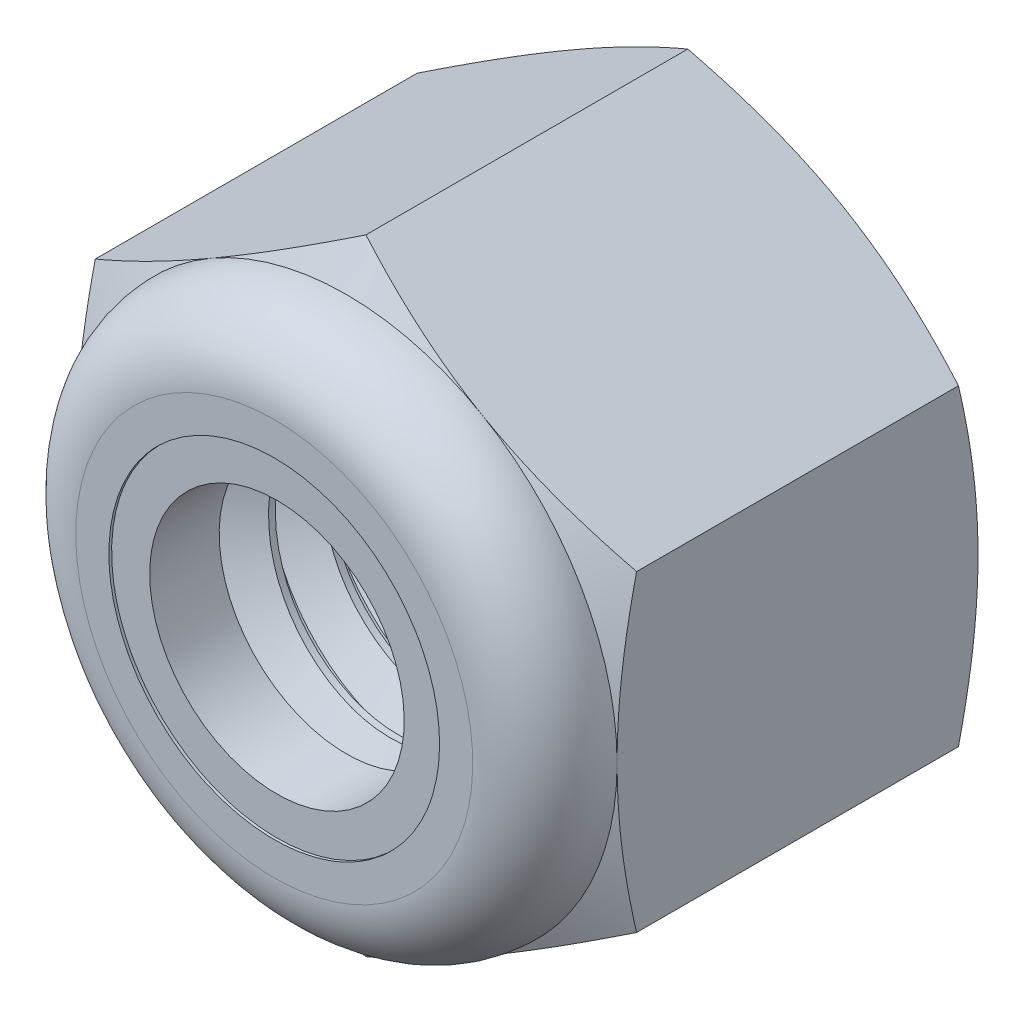
SolidWorks part; units mm, degrees
ref_plane "Front Plane" through (0, 0, 0) normal (0, 0, 1) x (1, 0, 0)
ref_plane "Top Plane" through (0, 0, 0) normal (0, 1, 0) x (1, 0, 0)
ref_plane "Right Plane" through (0, 0, 0) normal (1, 0, 0) x (0, 0, -1)
sketch "Sketch1" plane through (0, 0, 0) normal (0, 0, 1) x (1, 0, 0)
  line L1 (0, 5.7735) -> (-5, 2.8868)
  line L2 (-5, 2.8868) -> (-5, -2.8868)
  line L3 (-5, -2.8868) -> (0, -5.7735)
  line L4 (0, -5.7735) -> (5, -2.8868)
  line L5 (5, -2.8868) -> (5, 2.8868)
  line L6 (5, 2.8868) -> (0, 5.7735)
  circle A0 centre (0, 0) radius 5 construction
  circle A1 centre (0, 0) radius 3
  point P10 (0, -3)
  point P11 (0, 3)
  point P12 (0, 5)
  dimension "Thread Size" = 6
  dimension "Width" = 10
sketch "Sketch2" plane through (0, 0, 0) normal (1, 0, 0) x (0, 0, -1)
  line L0 (4, 0) -> (-4, 0) construction
  line L1 (-4, 3) -> (4, 3) construction
  line L2 (-3.95, -3.0086) -> (-5.27, -3.0086) construction
  line L3 (-4.9375, 3.1083) -> (-3.9375, 3.1083) construction
  line L4 (-3.9375, 3.1083) -> (-4.4375, 2.2422) construction
  line L5 (-4.4375, 2.2422) -> (-4.9375, 3.1083) construction
  line L6 (-4.875, 3) -> (-4, 3) construction
  line L7 (-4.5, 2.3505) -> (-4.375, 2.3505) construction
  line L8 (-4.4375, 2.3505) -> (-4.4375, 2.2422) construction
  line L9 (-4.4375, 3) -> (-4.4375, 3.1083) construction
  line L10 (-3.9687, 3.0541) -> (-4.9063, 3.0541)
  line L11 (-4.9063, 3.0541) -> (-4.5, 2.3505)
  line L12 (-4.5, 2.3505) -> (-4.375, 2.3505)
  line L13 (-4.375, 2.3505) -> (-3.9687, 3.0541)
  line L14 (4, 0) -> (5.27, 0)
  line L15 (5.27, 0) -> (5.27, 7.0435)
  line L16 (0, 7.0435) -> (0, 5.7735) construction
  line L17 (0, 5.7735) -> (0, 2.8868) construction
  line L18 (4, 5) -> (-2.6667, 5) construction
  line L19 (-4.5, -2.3505) -> (-4.375, -2.3505) construction
  line L20 (4, 5) -> (4, 0)
  line L21 (3.6393, 5.7735) -> (-2.306, 5.7735)
  line L22 (4, 5) -> (3.6393, 5.7735)
  line L23 (-4, 0) -> (-4, 3.6667) construction
  line L24 (-2.6667, 5) -> (-2.306, 5.7735)
  line L25 (5.27, 7.0435) -> (-5.27, 7.0435)
  line L26 (-4, 3.6667) -> (-5.27, 3.6667)
  line L27 (-5.27, 3.6667) -> (-5.27, 7.0435)
  line L28 (-3.95, 3.6667) -> (-3.95, 2.3505) construction
  line L29 (-3.95, 3.0086) -> (-5.27, 3.0086)
  line L30 (-5.27, 3.0086) -> (-5.27, 0)
  line L31 (-5.27, 0) -> (-2.6667, 0)
  line L32 (-2.6667, 0) -> (-2.6667, 4.95)
  line L33 (-3.95, 3.0086) -> (-3.95, 3.6667)
  arc A0 (-2.6667, 5) -> (-4, 3.6667) centre (-2.6667, 3.6667) ccw
  arc A1 (-2.6667, 4.95) -> (-3.95, 3.6667) centre (-2.6667, 3.6667) ccw
  point P4 (0, 0)
  point P18 (-4.4375, 3.0541)
  point P22 (-4.4375, 3.0541)
  point P33 (0, 5.7735)
  point P48 (-5.27, -3.0086)
  point P51 (-4.5, -2.3505)
  dimension "Height" = 8
  dimension "Pitch" = 1
  dimension "D1" = 0.125
  dimension "D2" = 1.27
  dimension "D3" = 25
  dimension "D4" = 1.3333
  dimension "D5" = 25
  dimension "D6" = 0.05
sketch "Sketch3" plane through (0, 0, 0) normal (0, 0, 1) x (1, 0, 0)
  line L0 (0, -5.7735) -> (5, -2.8868) construction
  line L1 (5, -2.8868) -> (5, 2.8868) construction
  line L2 (5, 2.8868) -> (0, 5.7735) construction
  line L3 (0, 5.7735) -> (-5, 2.8868) construction
  line L4 (-5, 2.8868) -> (-5, -2.8868) construction
  line L5 (-5, -2.8868) -> (0, -5.7735) construction
  line L6 (0, -5.7735) -> (5, -2.8868)
  line L7 (5, -2.8868) -> (5, 2.8868)
  line L8 (5, 2.8868) -> (0, 5.7735)
  line L9 (0, 5.7735) -> (-5, 2.8868)
  line L10 (-5, 2.8868) -> (-5, -2.8868)
  line L11 (-5, -2.8868) -> (0, -5.7735)
  circle A0 centre (0, 0) radius 3 construction
  circle A1 centre (0, 0) radius 3
extrude "Boss-Extrude1" add sketch "Sketch3" along normal mid plane 8
sketch "Sketch4" plane through (0, 0, 0) normal (1, 0, 0) x (0, 0, -1)
  line L0 (5.27, 7.0435) -> (-5.27, 7.0435) construction
  line L1 (-5.27, 3.6667) -> (-5.27, 7.0435) construction
  line L2 (-4, 3.6667) -> (-5.27, 3.6667) construction
  line L3 (-2.6667, 5) -> (-2.306, 5.7735) construction
  line L4 (3.6393, 5.7735) -> (-2.306, 5.7735) construction
  line L5 (4, 5) -> (3.6393, 5.7735) construction
  line L6 (4, 5) -> (4, 0) construction
  line L7 (4, 0) -> (5.27, 0) construction
  line L8 (5.27, 0) -> (5.27, 7.0435) construction
  line L9 (-5.27, 3.0086) -> (-5.27, 0) construction
  line L10 (-5.27, 0) -> (-2.6667, 0) construction
  line L11 (-2.6667, 0) -> (-2.6667, 4.95) construction
  line L12 (-3.95, 3.0086) -> (-3.95, 3.6667) construction
  line L13 (-3.95, 3.0086) -> (-5.27, 3.0086) construction
  line L14 (5.27, 7.0435) -> (-5.27, 7.0435)
  line L15 (-5.27, 3.6667) -> (-5.27, 7.0435)
  line L16 (-4, 3.6667) -> (-5.27, 3.6667)
  line L17 (-2.6667, 5) -> (-2.306, 5.7735)
  line L18 (3.6393, 5.7735) -> (-2.306, 5.7735)
  line L19 (4, 5) -> (3.6393, 5.7735)
  line L20 (4, 5) -> (4, 0)
  line L21 (4, 0) -> (5.27, 0)
  line L22 (5.27, 0) -> (5.27, 7.0435)
  line L23 (-5.27, 3.0086) -> (-5.27, 0)
  line L24 (-5.27, 0) -> (-2.6667, 0)
  line L25 (-2.6667, 0) -> (-2.6667, 4.95)
  line L26 (-3.95, 3.0086) -> (-3.95, 3.6667)
  line L27 (-3.95, 3.0086) -> (-5.27, 3.0086)
  arc A0 (-2.6667, 5) -> (-4, 3.6667) centre (-2.6667, 3.6667) ccw construction
  arc A1 (-2.6667, 4.95) -> (-3.95, 3.6667) centre (-2.6667, 3.6667) ccw construction
  arc A2 (-2.6667, 5) -> (-4, 3.6667) centre (-2.6667, 3.6667) ccw
  arc A3 (-2.6667, 4.95) -> (-3.95, 3.6667) centre (-2.6667, 3.6667) ccw
revolve "Cut-Revolve1" cut sketch "Sketch4" angle 360 about L0
sketch "Sketch5" plane through (0, 0, 0) normal (1, 0, 0) x (0, 0, -1)
  line L0 (-3.95, 3.6667) -> (-3.95, 2.3505) construction
  line L1 (-2.6667, 0) -> (-2.6667, 4.95) construction
  line L2 (-3.95, 3.6667) -> (-3.95, 2.3505)
  line L3 (-2.6667, 2.3505) -> (-2.6667, 4.95)
  line L4 (-3.95, 2.3505) -> (-2.6667, 2.3505)
  arc A0 (-2.6667, 4.95) -> (-3.95, 3.6667) centre (-2.6667, 3.6667) ccw construction
  arc A1 (-2.6667, 4.95) -> (-3.95, 3.6667) centre (-2.6667, 3.6667) ccw
revolve "Revolve1" add sketch "Sketch5" angle 360 about L0
sketch "Sketch6" plane through (0, 0, 4) normal (0, 0, 1) x (1, 0, 0)
  circle A0 centre (0, 0) radius 3 construction
  circle A1 centre (0, 0) radius 3
curve "Helix/Spiral1" pitch 1 height 9 radius 3 centre (0, 0, 4) axis (0, 0, -1) start towards (0, 1, 0)
sketch "Sketch7" plane through (0, 0, 0) normal (1, 0, 0) x (0, 0, -1)
  line L0 (-4.9063, 3.0541) -> (-4.5, 2.3505) construction
  line L1 (-4.5, 2.3505) -> (-4.375, 2.3505) construction
  line L2 (-4.375, 2.3505) -> (-3.9687, 3.0541) construction
  line L3 (-3.9687, 3.0541) -> (-4.9063, 3.0541) construction
  line L4 (-4.9063, 3.0541) -> (-4.5, 2.3505)
  line L5 (-4.5, 2.3505) -> (-4.375, 2.3505)
  line L6 (-4.375, 2.3505) -> (-3.9687, 3.0541)
  line L7 (-3.9687, 3.0541) -> (-4.9063, 3.0541)
sweep "Sweep1" add profiles "Sketch7" path "Helix/Spiral1"
sketch "Sketch8" plane through (0, 0, -4) normal (0, 0, -1) x (-1, 0, 0)
  circle A2 centre (0, 0) radius 3.0541
  point P2 (0, 3.0541)
extrude "Cut-Extrude1" cut sketch "Sketch8" along normal through all and the other way through all draft 60
sketch "Sketch9" plane through (0, 0, 2.6667) normal (0, 0, 1) x (1, 0, 0)
  circle A2 centre (0, 0) radius 3.0541
  circle A3 centre (0, 0) radius 2.3505 construction
  point P2 (0, 3.0541)
  point P4 (0, 2.3505)
extrude "Cut-Extrude2" cut sketch "Sketch9" along normal through all and the other way through all draft 60
equation "\"D1@Sketch2\" = \"Pitch@Sketch2\" / 8"
equation "\"D4@Sketch2\"=\"Height@Sketch2\"/6"
equation "\"D1@Boss-Extrude1\"=\"Height@Sketch2\""
equation "\"D3@Helix/Spiral1\"=\"Height@Sketch2\"+\"Pitch@Sketch2\""
equation "\"D4@Helix/Spiral1\"=\"Pitch@Sketch2\""
equation "\"D6@Sketch2\"=\"Pitch@Sketch2\"*0.05"
